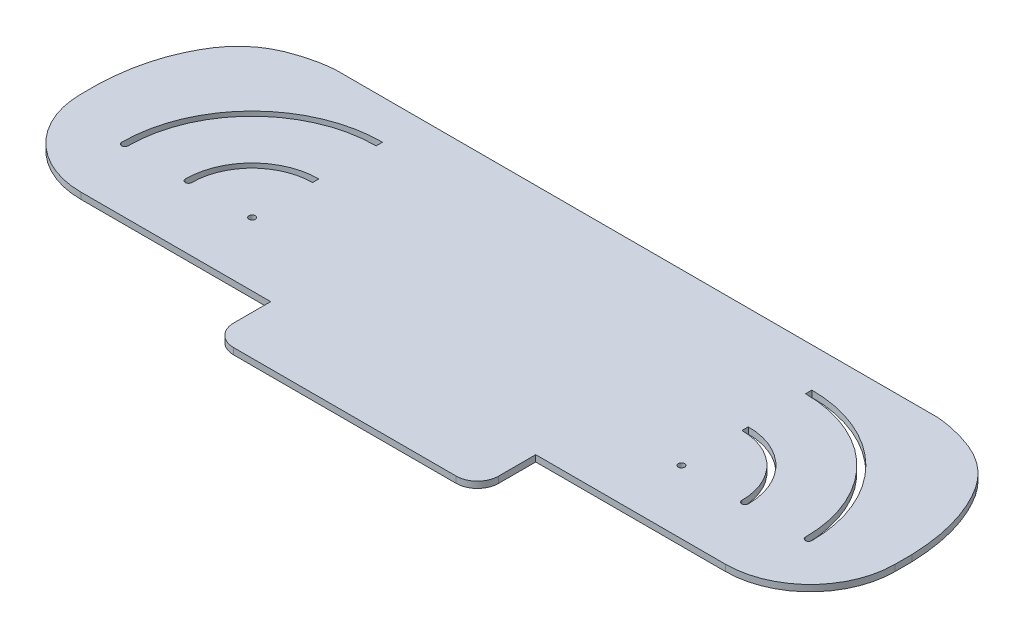
SolidWorks part; units mm, degrees
material "Thornel Mat VMA"
ref_plane "Front Plane" through (0, 0, 0) normal (0, 0, 1) x (1, 0, 0)
ref_plane "Top Plane" through (0, 0, 0) normal (0, 1, 0) x (1, 0, 0)
ref_plane "Right Plane" through (0, 0, 0) normal (1, 0, 0) x (0, 0, -1)
sketch "Sketch1" plane through (0, 0, 0) normal (0, 1, 0) x (1, 0, 0)
  line L0 (-62.5, -13.75) -> (-62.5, 13.75)
  line L1 (-62.5, -13.75) -> (62.5, -13.75)
  line L2 (-62.5, 13.75) -> (62.5, 13.75)
  line L3 (62.5, -13.75) -> (62.5, 13.75)
  line L4 (-62.5, -13.75) -> (62.5, 13.75) construction
  line L5 (-62.5, 13.75) -> (62.5, -13.75) construction
  point P1 (0, 0)
  dimension "D1" = 125
  dimension "D2" = 27.5
extrude "Boss-Extrude1" add sketch "Sketch1" along normal blind 1.5 and the other way blind 1.5
fillet "Fillet1" radius 10 1 edges at (-62.5, 0, 13.75) type face fillet first side face at (0, 0, 13.75) second side face at (-62.5, 0, 0)
fillet "Fillet2" radius 10 1 edges at (62.5, 0, 13.75) type face fillet first side face at (5, 0, 13.75) second side face at (62.5, 0, 0)
sketch "Sketch3" plane through (0, 0, 0) normal (0, 1, 0) x (1, 0, 0)
  line L0 (0, 0) -> (0, 13.75)
  line L1 (62.5, 13.75) -> (-62.5, 13.75) construction
  line L2 (0, 13.75) -> (0, 68.75)
  line L3 (-192, 123.75) -> (-192, 13.75)
  line L4 (-192, 123.75) -> (192, 123.75)
  line L5 (-192, 13.75) -> (192, 13.75)
  line L6 (192, 123.75) -> (192, 13.75)
  line L7 (-192, 123.75) -> (192, 13.75) construction
  line L8 (-192, 13.75) -> (192, 123.75) construction
  dimension "D1" = 55
  dimension "D2" = 384
extrude "Boss-Extrude2" add sketch "Sketch3" along normal up to surface (1.5 mm away) and the other way blind 1.5 contours L6 L4 L3 L5 region at (0, 0, -119.7556) up to face at (0, 1.5, 1.9404)
fillet "Fillet3" radius 40 1 edges at (192, 0, -13.75) type face fillet first side face at (127.25, 0, -13.75) second side face at (192, 0, -68.75)
fillet "Fillet4" radius 40 1 edges at (-192, 0, -13.75) type face fillet first side face at (-127.25, 0, -13.75) second side face at (-192, 0, -68.75)
sketch "Sketch4" plane through (0, 1.5, 0) normal (0, 1, 0) x (1, 0, 0)
  line L0 (-192, 123.75) -> (-142, 123.75)
  line L1 (-192, 123.75) -> (192, 123.75) construction
  line L2 (-192, 123.75) -> (-192, 53.75)
  line L3 (-192, 123.75) -> (-192, 53.75) construction
  line L4 (-192, 53.75) -> (-172, 53.75)
  line L5 (-172, 53.75) -> (-172, 113.75)
  spline S0 degree 2 poles (-192, 53.75) (-193.5369, 100.3799) (-160.3906, 123.75) knots 0 0 0 1 1 1
  spline S1 degree 2 poles (-172, 113.75) (-152.5677, 125.4979) (-130.9453, 123.75) knots 0 0 0 1 1 1
  line M5 (-192, 123.75) -> (-192, 53.75)
  line M16 (192, 123.75) -> (-192, 123.75)
  dimension "D1" = 50
  dimension "D2" = 70
  dimension "D3" = 20
  dimension "D4" = 60
extrude "Cut-Extrude1" cut sketch "Sketch4" against normal through all contours S0 L0 M5 | S0 S1 M16 region at (-183.1076, 1.5, -108.8867) region at (-159.3887, 1.5, -120.9444)
fillet "Fillet5" radius 40 1 edges at (-172, 0, -113.75) type face fillet first side face at (-164.5, 0, -116.25) second side face at (-187, 0, -74.812)
mirror "Mirror1" about plane through (0, 0, 0) normal (1, 0, 0) of "Fillet5", "Cut-Extrude1"
sketch "Sketch5" plane through (0, 1.5, 0) normal (0, 1, 0) x (1, 0, 0)
  line L0 (0, -13.75) -> (-62.5, 13.75)
  line L1 (-52.5, -13.75) -> (52.5, -13.75) construction
  line L2 (-62.5, 13.75) -> (0, 13.75)
  line L3 (0, 13.75) -> (0, 43.75)
  line L4 (0, 43.75) -> (-101.25, 43.75)
  line L5 (-101.25, 43.75) -> (-131.25, 43.75)
  line L6 (-131.25, 43.75) -> (-161.25, 43.75)
  line L7 (-101.25, 43.75) -> (-101.25, 73.75)
  line L8 (-101.25, 73.75) -> (-101.25, 103.75)
  circle A0 centre (-101.25, 43.75) radius 1.5
  circle A1 centre (-131.25, 43.75) radius 1.5
  circle A2 centre (-161.25, 43.75) radius 1.5
  circle A3 centre (-101.25, 73.75) radius 1.5
  circle A4 centre (-101.25, 103.75) radius 1.5
  dimension "D3" = 3
  dimension "D5" = 3
  dimension "D7" = 3
  dimension "D10" = 3
  dimension "D11" = 3
  dimension "D1" = 30
  dimension "D2" = 101.25
  dimension "D4" = 30
  dimension "D6" = 30
  dimension "D8" = 30
  dimension "D9" = 30
extrude "Cut-Extrude2" cut sketch "Sketch5" against normal through all contours A1 | A0 | A2
ref_axis "Axis1" through (-101.25, -1.5, -43.75) along (0, 1, 0)
ref_plane "Plane1" through (0, 0, -43.75) normal (0, 0, 1) x (1, 0, 0)
sketch "Sketch8" plane through (0, 0, -43.75) normal (0, 0, 1) x (1, 0, 0)
  line L0 (0, 0) -> (-131.25, 0)
  line L1 (-131.25, 0) -> (-161.25, 0)
  line L2 (-132.75, 1.5) -> (-132.75, -1.5)
  line L3 (-132.75, 1.5) -> (-129.75, 1.5)
  line L4 (-132.75, -1.5) -> (-129.75, -1.5)
  line L5 (-129.75, 1.5) -> (-129.75, -1.5)
  line L6 (-132.75, 1.5) -> (-129.75, -1.5) construction
  line L7 (-132.75, -1.5) -> (-129.75, 1.5) construction
  line L8 (-162.75, 1.5) -> (-159.75, 1.5)
  line L9 (-162.75, 1.5) -> (-162.75, -1.5)
  line L10 (-159.75, 1.5) -> (-159.75, -1.5)
  line L11 (-162.75, -1.5) -> (-159.75, -1.5)
  dimension "D1" = 131.25
  dimension "D2" = 30
  dimension "D3" = 3
  dimension "D4" = 3
  dimension "D5" = 2
revolve "Cut-Revolve1" cut sketch "Sketch8" angle 90 about axis through (-101.25, -1.5, -43.75) along (0, 1, 0) reverse direction yes
mirror "Mirror2" about plane through (0, 0, 0) normal (1, 0, 0) of "Cut-Revolve1", "Cut-Extrude2"
